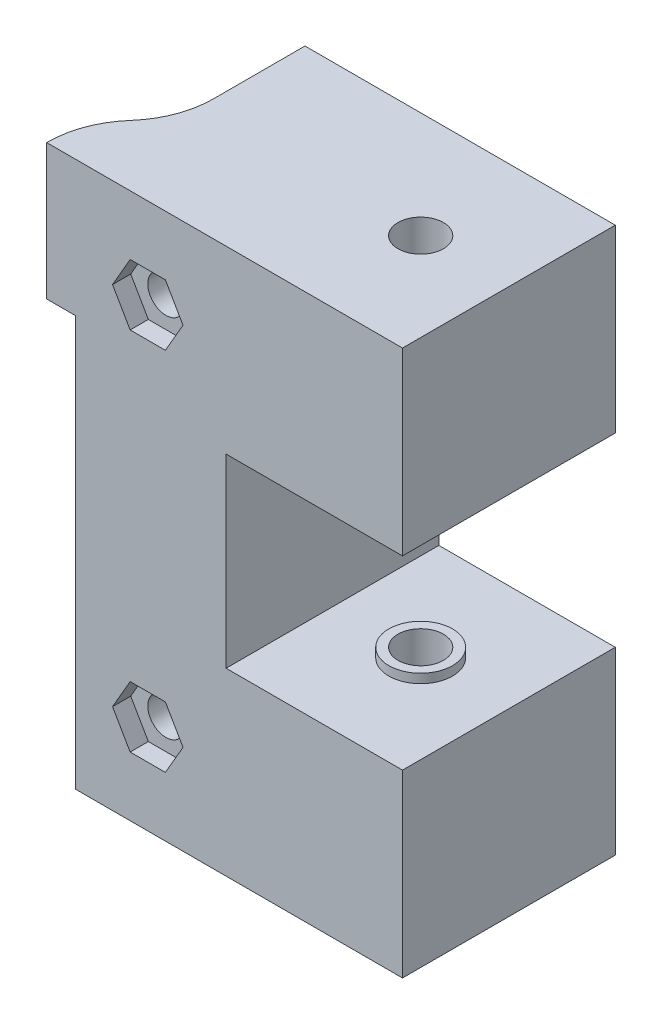
SolidWorks part; units mm, degrees
ref_plane "Front Plane" through (0, 0, 0) normal (0, 0, 1) x (1, 0, 0)
ref_plane "Top Plane" through (0, 0, 0) normal (0, 1, 0) x (1, 0, 0)
ref_plane "Right Plane" through (0, 0, 0) normal (1, 0, 0) x (0, 0, -1)
sketch "MainBlock" plane through (0, 0, 0) normal (0, 0, 1) x (1, 0, 0)
  line L0 (0, 0) -> (39.125, 0)
  line L1 (39.125, 0) -> (39.125, 19.8)
  line L2 (39.125, 19.8) -> (19.725, 19.8)
  line L3 (19.725, 19.8) -> (19.725, 40.2)
  line L4 (19.725, 40.2) -> (39.125, 40.2)
  line L5 (39.125, 40.2) -> (39.125, 60)
  line L6 (39.125, 60) -> (0, 60)
  line L7 (0, 60) -> (0, 0)
  circle A0 centre (11.1125, 50.1) radius 2
  circle A1 centre (11.1125, 9.9) radius 2
  dimension "D4" = 4
  dimension "D1" = 39.125
  dimension "D2" = 60
  dimension "D3" = 20.4
  dimension "D5" = 19.4
  dimension "D6" = 11.1125
  dimension "D7" = 9.9
  dimension "D8" = 9.9
  dimension "D9" = 19.8
  dimension "D10" = 19.8
extrude "MainBlockBoss-Extrude1" add sketch "MainBlock" along normal blind 23.4
sketch "TopHoleCut-Sketch2" plane through (0, 60, 0) normal (0, 1, 0) x (1, 0, 0)
  line L0 (39.125, 0) -> (0, 0) construction
  circle A0 centre (29.425, -11.7) radius 2.5
  dimension "D3" = 5
  dimension "D1" = 11.7
  dimension "D2" = 9.7
extrude "TopHoleCut-Extrude1" cut sketch "TopHoleCut-Sketch2" against normal blind 45
sketch "MountHoleBoreSketch3" plane through (0, 0, 23.4) normal (0, 0, 1) x (1, 0, 0)
  line L1 (14.9875, 50.1) -> (13.05, 53.4558)
  line L2 (13.05, 53.4558) -> (9.175, 53.4558)
  line L3 (9.175, 53.4558) -> (7.2375, 50.1)
  line L4 (7.2375, 50.1) -> (9.175, 46.7442)
  line L5 (9.175, 46.7442) -> (13.05, 46.7442)
  line L6 (13.05, 46.7442) -> (14.9875, 50.1)
  line L7 (14.9875, 9.9) -> (13.05, 13.2558)
  line L8 (13.05, 13.2558) -> (9.175, 13.2558)
  line L9 (9.175, 13.2558) -> (7.2375, 9.9)
  line L10 (7.2375, 9.9) -> (9.175, 6.5442)
  line L11 (9.175, 6.5442) -> (13.05, 6.5442)
  line L12 (13.05, 6.5442) -> (14.9875, 9.9)
  circle A0 centre (11.1125, 50.1) radius 3.3558 construction
  circle A1 centre (11.1125, 9.9) radius 3.3558 construction
  point P10 (11.1125, 53.4558)
  dimension "D1" = 7.75
extrude "MountHoleBoreCut-Extrude2" cut sketch "MountHoleBoreSketch3" against normal blind 2
sketch "TopSpacerSketch4" plane through (0, 40.2, 0) normal (0, -1, 0) x (1, 0, 0)
  circle A0 centre (29.425, 11.7) radius 3.5
  circle A1 centre (29.425, 11.7) radius 2.5
  circle A2 centre (29.425, 11.7) radius 2.5 construction
  dimension "D1" = 7
extrude "TopSpacerBoss-Extrude2" add sketch "TopSpacerSketch4" along normal blind 1
sketch "LowerSpacerSketch5" plane through (0, 19.8, 0) normal (0, 1, 0) x (1, 0, 0)
  circle A0 centre (29.425, -11.7) radius 2.5
  circle A1 centre (29.425, -11.7) radius 2.5 construction
  circle A2 centre (29.425, -11.7) radius 3.5
  circle A3 centre (29.425, -11.7) radius 3.5 construction
extrude "LowerSpacerBoss-Extrude3" add sketch "LowerSpacerSketch5" along normal blind 1
sketch "PushPinHoleSketch1" plane through (0, 0, 0) normal (0, -1, 0) x (1, 0, 0)
  circle A0 centre (29.425, 11.7) radius 1
  circle A1 centre (29.425, 11.7) radius 2.5 construction
  dimension "D1" = 2
extrude "PushPinHoleCut-Extrude1" cut sketch "PushPinHoleSketch1" against normal through all
sketch "ScrewCollisionSketch2" plane through (0, 0, 0) normal (-1, 0, 0) x (0, 0, 1)
  line L0 (0, 60) -> (0, 0) construction
  line L1 (0, 60) -> (18.72, 60)
  line L2 (0, 60) -> (0, 0)
  line L3 (0, 0) -> (18.72, 0)
  line L4 (18.72, 60) -> (18.72, 0)
  line L5 (23.4, 0) -> (0, 0) construction
  dimension "D1" = 18.72
extrude "ScrewCollisionCut-Extrude2" cut sketch "ScrewCollisionSketch2" against normal blind 5
fillet "ScrewCollisionFillet1" radius 10 1 edges at (5, 30, 18.72)
fillet "ScrewCollisionFillet2" radius 10 1 edges at (0, 30, 18.72)
sketch "MidRailIndentSketch1" plane through (0, 0, 23.4) normal (0, 0, 1) x (1, 0, 0)
  line L0 (0, 60) -> (0, 0) construction
  line L1 (0, 45.1) -> (3.175, 45.1)
  line L2 (0, 45.1) -> (0, 0)
  line L3 (0, 0) -> (3.175, 0)
  line L4 (3.175, 45.1) -> (3.175, 0)
  line L5 (39.125, 60) -> (0, 60) construction
  line L6 (0, 0) -> (39.125, 0) construction
  dimension "D1" = 14.9
  dimension "D3" = 3.175
extrude "MidRailIndentCut-Extrude1" cut sketch "MidRailIndentSketch1" against normal through all
equation "\"BeltTensionerWidth\"= \"MidRailToAlignWithGantryBlock\" + \"BeltTensionerInnerWidth\" / 2 + \"RailThickness\""
equation "\"BeltTensionerHeight\"= 60mm"
equation "\"BeltTensionerDepth\"= \"BeltTensionerBackWallThickness\" + \"BeltTensionerInnerDepth\"'Equals 23.4"
equation "\"BeltTensionerInnerWidth\"= \"20TGT2PulleyDiameter\" + \"BeltTensionerSpaceBetweenPulleyAndWall\""
equation "\"BeltTensionerInnerHeight\"= \"20TGT2PulleyWidth\" * 2 + \"1mmSpacer\" * 3"
equation "\"BeltTensionerBackWallThickness\"= 4mm"
equation "\"BeltTensionerInnerDepth\"= \"20TGT2PulleyDiameter\" + \"BeltTensionerSpaceBetweenPulleyAndWall\""
equation "\"RailThickness\"= .125in'Spec"
equation "\"HoleOffsetFromEdge\"= \"RailThickness\" * 2.5"
equation "\"LinearGBWithRailDepth\"= 12.75mm'Spec"
equation "\"GABDistanceFromBackToFirstPulley\"= 13.5mm"
equation "\"MidRailToAlignWithGantryBlock\"= \"LinearGBWithRailDepth\" + \"GABDistanceFromBackToFirstPulley\"'All outside cogs must align"
equation "\"20TGT2PulleyDiameter\"= 17.9mm'Spec"
equation "\"BeltTensionerSpaceBetweenPulleyAndWall\"= 1.5mm"
equation "\"BeltTensionerMountingHoleDiameter\"= 4.0mm"
equation "\"BeltTensionerMountingHoleOffsetFromTopOrBottom\"= ( \"BeltTensionerHeight\" - \"BeltTensionerInnerHeight\" ) / 4"
equation "\"20TGT2PulleyWidth\"= 8.7mm'The STL of the Pulley in the diagram is a bit larger"
equation "\"1mmSpacer\"= 1mm"
equation "\"SteelShaft5mmHoleDiameter\"= 5mm"
equation "\"BeltTensionerMountingHoleOuterBoreDepth\"= 2mm"
equation "\"BeltTensionerMountingHoleOuterBoreDiameter\"= 7.75mm"
equation "\"7mmx1mmSpacerDiameter\"= 7mm"
equation "\"7mmx1mmSpacerHeight\"= 1mm"
equation "\"D1@MainBlock\" = \"BeltTensionerWidth\""
equation "\"D4@MainBlock\" = \"BeltTensionerMountingHoleDiameter\""
equation "\"D5@MainBlock\" = \"BeltTensionerInnerWidth\""
equation "\"D6@MainBlock\"=\"HoleOffsetFromEdge\" + \"RailThickness\""
equation "\"D7@MainBlock\"=\"BeltTensionerMountingHoleOffsetFromTopOrBottom\""
equation "\"D8@MainBlock\"=\"BeltTensionerMountingHoleOffsetFromTopOrBottom\""
equation "\"D1@MainBlockBoss-Extrude1\" = \"BeltTensionerDepth\""
equation "\"D1@TopHoleCut-Sketch2\" = \"BeltTensionerDepth\" / 2"
equation "\"D3@TopHoleCut-Sketch2\" = \"SteelShaft5mmHoleDiameter\""
equation "\"D1@MountHoleBoreSketch3\" = \"BeltTensionerMountingHoleOuterBoreDiameter\""
equation "\"D1@MountHoleBoreCut-Extrude2\"=\"BeltTensionerMountingHoleOuterBoreDepth\""
equation "\"D1@TopSpacerSketch4\" = \"7mmx1mmSpacerDiameter\""
equation "\"D1@TopSpacerBoss-Extrude2\" = \"7mmx1mmSpacerHeight\""
equation "\"D1@LowerSpacerBoss-Extrude3\" = \"7mmx1mmSpacerHeight\""
equation "\"SteelPinPushHoleDiameter\"= 2mm"
equation "\"D1@PushPinHoleSketch1\" = \"SteelPinPushHoleDiameter\""
equation "\"BeltTensionerSteelShaftHoleDepthFromTop\"= ( \"SteelShaftLength\" - \"BeltTensionerInnerHeight\" ) / 2 + ( \"BeltTensionerHeight\" - \"BeltTensionerInnerHeight\" ) / 2 + \"BeltTensionerInnerHeight\"'Equals 45"
equation "\"SteelShaftLength\"= 30mm"
equation "\"D1@TopHoleCut-Extrude1\"=\"BeltTensionerSteelShaftHoleDepthFromTop\""
equation "\"D2@TopHoleCut-Sketch2\"=\"BeltTensionerWidth\" -\"MidRailToAlignWithGantryBlock\" - \"RailThickness\""
equation "\"D1@ScrewCollisionSketch2\" = \"BeltTensionerDepth\" * .8"
equation "\"D3@MidRailIndentSketch1\" = \"RailThickness\""
equation "\"D1@MidRailIndentSketch1\"=\"DistanceAboveMidSideRailToBeltTensioner\""
equation "\"LinearRailWidth\"= 12mm'Spec"
equation "\"MidSideRailVerticalOffset\"= \"LinearRailWidth\" + 3mm'Allows space for RodStabilizer to attach to bottom of MidSideRail"
equation "\"DistanceAboveMidSideRailToBeltTensioner\"= \"VS ToTopOfBeltTensionerAlignedWithYAxisGantryBlockUpperPulley\" - \"V8 ToTopOfMidSideRail\"'Equals 14.9"
equation "\"DistanceFromBeltTensionerTopPulleyToBeltTensionerTop\"= \"7mmx1mmSpacerHeight\" + \"BeltTensionerTopHeight\"'Equals 20.8"
equation "\"BeltTensionerTopHeight\"= ( \"BeltTensionerHeight\" - \"BeltTensionerInnerHeight\" ) / 2'Equals 19.8"
equation "\"GABUpperHeight\"= 4mm"
equation "\"D9@MainBlock\"=\"BeltTensionerTopHeight\""
equation "\"D3@MainBlock\"=\"BeltTensionerInnerHeight\""
equation "\"D2@MainBlock\"=\"BeltTensionerHeight\""
equation "\"LegHeight\"= 70mm'Space needed for PSU/Stepper/Electronics"
equation "\"V1 BottomOfLowerRail\"= \"LegHeight\""
equation "\"LowerEnclosureThickness\"= 5mm"
equation "\"StepperShaftLength\"= 24mm'Pulley will be attached to the end"
equation "\"ZAxisLeadScrewLength\"= 200mm"
equation "\"LM8UUHeight\"= 24mm'Spec"
equation "\"V2 ToBedAtTopOfZAxis\"= \"V1 BottomOfLowerRail\" - \"LowerEnclosureThickness\" + \"StepperShaftLength\" + \"ZAxisLeadScrewLength\" - \"LM8UUHeight\" / 2'Equals 277"
equation "\"BedToBuildPlateStandoffLength\"= 15mm"
equation "\"BuildPlateHeight\"= 8mm'Spec"
equation "\"V4 ToTopOfBuildPlate/HotEndTip\"= \"V2 ToBedAtTopOfZAxis\" + \"BedToBuildPlateStandoffLength\" + \"BuildPlateHeight\""
equation "\"HotEndToTopOfXAxisGB\"= 71.68487mm'Equals 71.68487. Measured after installed onto X-Axis linear rail guide block"
equation "\"LinearGBWidth\"= 27mm'Spec"
equation "\"TopOfGBToBottomOfLinearRail\"= \"LinearGBWidth\" / 2 + \"LinearRailWidth\" / 2'Equals 19.5"
equation "\"V5 ToBottomOfXAxisLinearRail\"= \"V4 ToTopOfBuildPlate/HotEndTip\" + \"HotEndToTopOfXAxisGB\" - \"TopOfGBToBottomOfLinearRail\"'Equals 352.18487"
equation "\"GABMidWallHeight\"= 28mm'Must equal 28 or changes alignment"
equation "\"GABLowerHeight\"= 4mm"
equation "\"GABHeight\"= \"GABLowerHeight\" + \"GABMidWallHeight\" + \"GABUpperHeight\""
equation "\"V6 ToMiddleOfYAxisGantryBlock\"= \"V5 ToBottomOfXAxisLinearRail\" - \"GABHeight\" / 2'Equals 334.18487"
equation "\"V8 ToTopOfMidSideRail\"= \"V6 ToMiddleOfYAxisGantryBlock\" + \"MidSideRailVerticalOffset\"'Equals 349.18487"
equation "\"VS ToTopOfBeltTensionerAlignedWithYAxisGantryBlockUpperPulley\"= \"V5 ToBottomOfXAxisLinearRail\" - \"DistanceFromXAxisLinearRailBottomAndTopOfGantryPulley\" + \"DistanceFromBeltTensionerTopPulleyToBeltTensionerTop\"'Equals 364.08487"
equation "\"DistanceFromXAxisLinearRailBottomAndTopOfGantryPulley\"= \"GABUpperHeight\" + \"GABMidShortRiserHeight\" - \"GABRiserBossOffset\"'Equals 8.9"
equation "\"GABMidShortRiserHeight\"= \"GABMidWallHeight\" / 2 - \"20TGT2PulleyWidth\"'Equals 5.3"
equation "\"GABRiserBossOffset\"= 0.4mm'Aligns Pulleys inside edges to be 2.5mm (.5mm apart top to bottom)"
